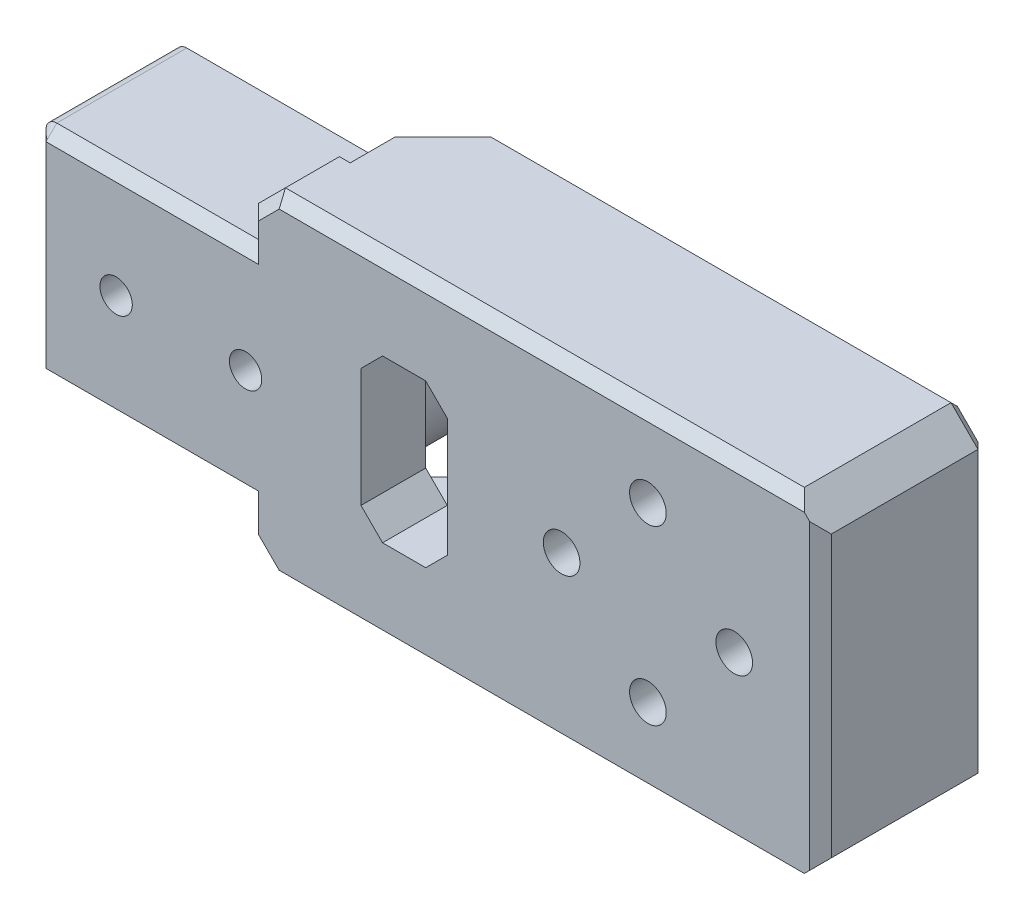
SolidWorks part; units mm, degrees
ref_plane "Front Plane" through (0, 0, 0) normal (0, 0, 1) x (1, 0, 0)
ref_plane "Top Plane" through (0, 0, 0) normal (0, 1, 0) x (1, 0, 0)
ref_plane "Right Plane" through (0, 0, 0) normal (1, 0, 0) x (0, 0, -1)
sketch "Sketch1" plane through (0, 0, 0) normal (0, 0, 1) x (1, 0, 0)
  line L1 (1, 0) -> (19.7, 0)
  line L2 (0, 1) -> (0, 19.2)
  line L3 (1, 20.2) -> (19.7, 20.2)
  arc A0 (19.7, 20.2) -> (19.7, 0) centre (19.7, 10.1) cw
  arc A1 (1, 0) -> (0, 1) centre (1, 1) cw
  arc A2 (0, 19.2) -> (1, 20.2) centre (1, 19.2) cw
  point P8 (0, 0)
  point P11 (0, 20.2)
  dimension "D3" = 1
  dimension "D1" = 19.7
  dimension "D2" = 20.2
extrude "Boss-Extrude1" add sketch "Sketch1" along normal blind 11
sketch "Sketch3" plane through (0, 0, 11) normal (0, 0, 1) x (1, 0, 0)
  line L0 (0, 19.2) -> (0, 1) construction
  line L1 (0, 16) -> (19.7, 16)
  line L2 (0, 16) -> (0, 4.2)
  line L3 (0, 4.2) -> (19.7, 4.2)
  line L5 (19.7, 20.2) -> (1, 20.2) construction
  arc A0 (19.7, 16) -> (19.7, 4.2) centre (19.7, 10.1) cw
  dimension "D1" = 5.9
  dimension "D2" = 19.7
  dimension "D3" = 4.2
extrude "Cut-Extrude2" cut sketch "Sketch3" against normal blind 8.05
ref_plane "Plane1" through (1, 0, 0) normal (-1, 0, 0) x (0, 0, 1)
sketch "Sketch4" plane through (1, 0, 0) normal (-1, 0, 0) x (0, 0, 1)
  line L0 (2.95, 16) -> (11, 16) construction
  line L1 (5.7, 16) -> (8.2, 16)
  line L2 (5.7, 16) -> (5.7, 14.5)
  line L3 (5.7, 14.5) -> (8.2, 14.5)
  line L4 (8.2, 16) -> (8.2, 14.5)
  line L5 (2.95, 4.2) -> (11, 4.2) construction
  line L6 (5.7, 4.2) -> (8.2, 4.2)
  line L7 (5.7, 4.2) -> (5.7, 5.7)
  line L8 (5.7, 5.7) -> (8.2, 5.7)
  line L9 (8.2, 4.2) -> (8.2, 5.7)
  line L10 (2.95, 16) -> (2.95, 4.2) construction
  dimension "D1" = 2.75
  dimension "D2" = 2.5
  dimension "D3" = 1.5
extrude "Boss-Extrude2" add sketch "Sketch4" against normal up to next
sketch "Sketch14" plane through (0, 0, 11) normal (0, 0, 1) x (1, 0, 0)
  line L0 (0, 19.2) -> (0, 1)
  line L1 (1, 0) -> (19.7, 0)
  line L2 (1, 0) -> (19.7, 0) construction
  line L3 (1, 20.2) -> (19.7, 20.2)
  arc A0 (0, 1) -> (1, 0) centre (1, 1) ccw construction
  arc A1 (19.7, 0) -> (19.7, 20.2) centre (19.7, 10.1) ccw construction
  arc A2 (19.7, 20.2) -> (19.7, 0) centre (19.7, 10.1) cw
  arc A3 (0, 19.2) -> (1, 20.2) centre (1, 19.2) cw
  arc A4 (0, 1) -> (1, 0) centre (1, 1) ccw
extrude "Boss-Extrude5" add sketch "Sketch14" along normal blind 3.05
fillet "Fillet3" radius 1 6 edges at (1, 15.25, 5.7) (1, 15.25, 8.2) (1, 5.7, 6.95) (1, 14.5, 6.95) (1, 4.95, 5.7) (1, 4.95, 8.2)
ref_plane "Plane2" through (19.7, 0, 0) normal (1, 0, 0) x (0, 0, -1)
sketch "Sketch8" plane through (0, 0, 14.05) normal (0, 0, -1) x (-1, 0, 0)
  line L0 (-19.7, 20.2) -> (-19.7, 16) construction
  line L2 (-19.7, 25.6) -> (-72.8, 25.6)
  line L3 (-72.8, 25.6) -> (-72.8, -5.4)
  line L4 (-72.8, -5.4) -> (-19.7, -5.4)
  line L5 (-29.8, 10.1) -> (-19.7, 10.1) construction
  line L6 (-64.8, 10.1) -> (-56.8, 10.1) construction
  line L7 (-72.8, 10.1) -> (-19.7, 10.1) construction
  line L8 (-19.7, 16) -> (-19.7, 4.2) construction
  line L9 (-19.7, 4.2) -> (-2, 4.2) construction
  line L10 (-19.7, 25.6) -> (-19.7, 16)
  line L12 (-19.7, 4.2) -> (-19.7, 0) construction
  line L13 (-19.7, 4.2) -> (-19.7, -5.4)
  arc A0 (-19.7, 20.2) -> (-19.7, 0) centre (-19.7, 10.1) ccw construction
  arc A5 (-19.7, 16) -> (-19.7, 4.2) centre (-19.7, 10.1) ccw
  circle A9 centre (-64.8, 10.1) radius 1.7
  circle A19 centre (-56.8, 2.1) radius 1.7
  circle A20 centre (-48.8, 10.1) radius 1.7
  circle A21 centre (-56.8, 18.1) radius 1.7
  point P15 (-64.8, 10.1)
  point P16 (-19.7, 10.1)
  point P21 (-56.8, 10.1)
  point P30 (-44.3, 10.1)
  point P37 (-56.8, 10.1)
  dimension "D3" = 8
  dimension "D1" = 5.9
  dimension "D5" = 3.4
  dimension "D2" = 31
  dimension "D4" = 8
  dimension "D7" = 53.1
  dimension "D6" = 4
extrude "Boss-Extrude3" add sketch "Sketch8" along normal blind 6
chamfer "Chamfer1" distance 2.5 angle 45 4 edges at (19.7, -5.4, 11.05) (72.8, -5.4, 11.05) (72.8, 25.6, 11.05) (19.7, 25.6, 11.05)
sketch "Sketch10" plane through (0, 0, 0) normal (0, 0, -1) x (-1, 0, 0)
  line L0 (0, 10.1) -> (-24.6007, 10.1) construction
  line L1 (0, 19.2) -> (0, 1) construction
  circle A0 centre (-7.5, 10.1) radius 1.7
  circle A1 centre (-19.5, 10.1) radius 1.7
  dimension "D3" = 3.4
  dimension "D4" = 3.4
  dimension "D1" = 7.5
  dimension "D2" = 12
extrude "Cut-Extrude5" cut sketch "Sketch10" against normal up to next
sketch "Sketch11" plane through (0, 0, 8.05) normal (0, 0, -1) x (-1, 0, 0)
  line L16 (-71.8, 10.1) -> (-19.5, 10.1) construction
  line L20 (-22.2, 25.6) -> (-70.3, 25.6)
  line L21 (-70.3, 25.6) -> (-72.8, 23.1)
  line L22 (-72.8, 23.1) -> (-72.8, -2.9)
  line L23 (-72.8, -2.9) -> (-70.3, -5.4)
  line L24 (-70.3, -5.4) -> (-22.2, -5.4)
  line L25 (-70.3, -5.4) -> (-22.2, -5.4) construction
  line L26 (-22.2, -5.4) -> (-22.2, -2.4)
  line L27 (-22.2, -2.4) -> (-68.8, -2.4)
  line L28 (-69.8, -1.4) -> (-69.8, 21.6)
  line L29 (-68.8, 22.6) -> (-22.2, 22.6)
  line L30 (-22.2, 22.6) -> (-22.2, 25.6)
  line L31 (-68.8, -2.4) -> (-69.8, -1.4)
  line L32 (-69.8, 21.6) -> (-68.8, 22.6)
  point P17 (-69.8, -2.4)
  point P19 (-69.8, 22.6)
  dimension "D1" = 3
  dimension "D2" = 3
  dimension "D3" = 3
extrude "Boss-Extrude4" add sketch "Sketch11" along normal blind 9.6
chamfer "Chamfer3" distance 5 angle 45 2 edges at (22.2, 24.1, -1.55) (22.2, -3.9, -1.55)
chamfer "Chamfer2" distance 1 angle 45 27 edges at (48.75, 25.6, -1.55) (46.25, -5.4, 14.05) (72.8, 10.1, 14.05) (46.25, 25.6, 14.05) (22.2, 25.6, 5.75) (22.2, -5.4, 5.75) (24.7, -5.4, 0.95) (24.7, 25.6, 0.95) (48.75, -5.4, -1.55) (71.55, -4.15, -1.55) (72.8, 10.1, -1.55) (71.55, 24.35, -1.55) (10.35, 0, 0) (29.8, 10.1, 0) (10.35, 20.2, 0) (0.2929, 19.9071, 0) (0.2929, 0.2929, 0) (0, 10.1, 14.05) (10.35, 0, 14.05) (19.7, -1.45, 14.05) (20.95, -4.15, 14.05) (0.2929, 0.2929, 14.05) (0.2929, 19.9071, 14.05) (10.35, 20.2, 14.05) (19.7, 21.65, 14.05) (20.95, 24.35, 14.05) (0, 10.1, 0)
sketch "Sketch12" plane through (0, 0, 8.05) normal (0, 0, -1) x (-1, 0, 0)
  line L0 (-69.8, 10.1) -> (-19.7, 10.1) construction
  line L15 (-50.8, 10.1) -> (-38.2, 10.1) construction
  line L16 (-38.2, 4.6) -> (-38.2, 15.6)
  line L20 (-69.8, -1.4) -> (-69.8, 21.6) construction
  line L21 (-36.2, 17.6) -> (-32.2, 17.6)
  line L22 (-30.2, 15.6) -> (-30.2, 4.6)
  line L23 (-19.7, 5.445) -> (-19.7, -5.445) construction
  line L24 (-38.2, 15.6) -> (-36.2, 17.6)
  line L25 (-32.2, 17.6) -> (-30.2, 15.6)
  line L26 (-32.2, 2.6) -> (-30.2, 4.6)
  line L27 (-36.2, 2.6) -> (-32.2, 2.6)
  line L28 (-38.2, 4.6) -> (-36.2, 2.6)
  circle A3 centre (-48.8, 10.1) radius 1.7 construction
  point P6 (-30.2, 17.6)
  point P7 (-38.2, 17.6)
  point P15 (-30.2, 10.1)
  dimension "D3" = 8
  dimension "D4" = 10.6
  dimension "D2" = 7.5
extrude "Cut-Extrude6" cut sketch "Sketch12" against normal through all both and the other way through all
sketch "Sketch15" plane through (0, 0, 0) normal (0, 0, -1) x (-1, 0, 0)
  circle A0 centre (-19.5, 10.1) radius 1.5
  circle A1 centre (-7.5, 10.1) radius 1.5
extrude "Cut-Extrude7" cut sketch "Sketch15" against normal through all
